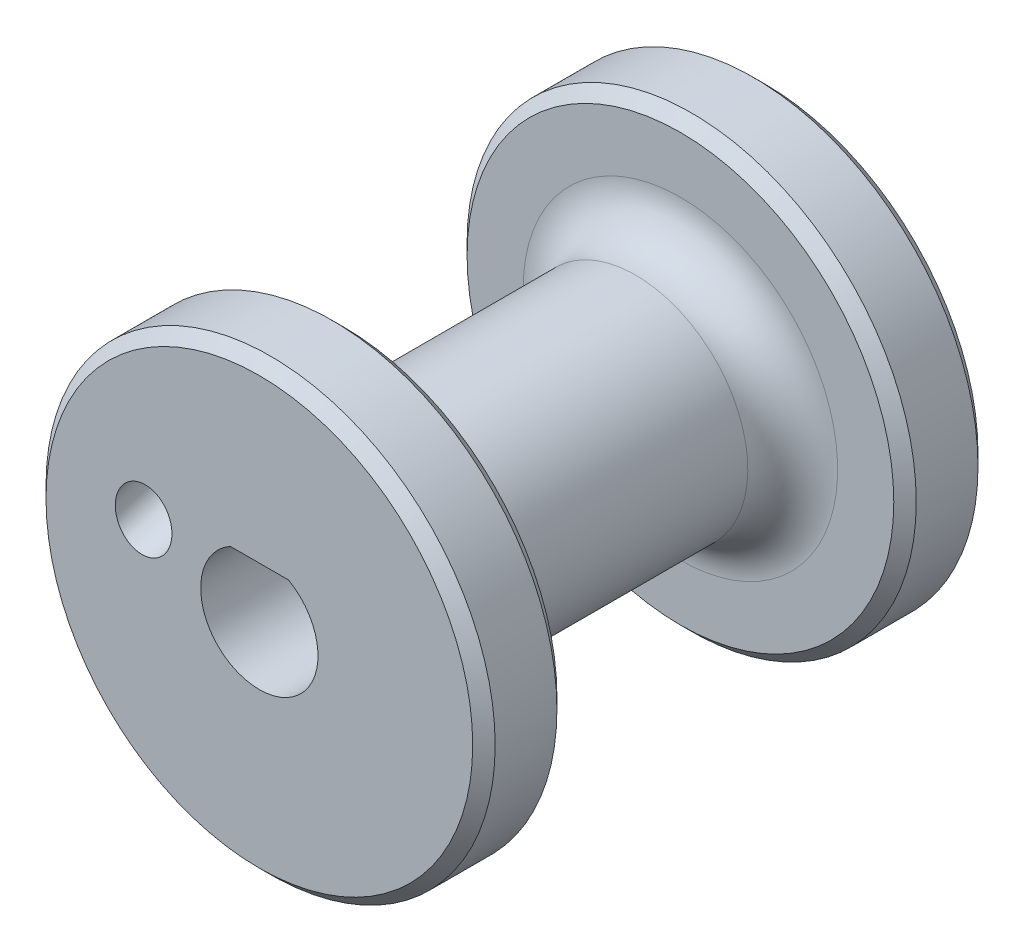
SolidWorks part; units mm, degrees
ref_plane "Front Plane" through (0, 0, 0) normal (0, 0, 1) x (1, 0, 0)
ref_plane "Top Plane" through (0, 0, 0) normal (0, 1, 0) x (1, 0, 0)
ref_plane "Right Plane" through (0, 0, 0) normal (1, 0, 0) x (0, 0, -1)
sketch "Sketch1" plane through (0, 0, 0) normal (0, 0, 1) x (1, 0, 0)
  circle A0 centre (0, 0) radius 3.3175
  circle A1 centre (0, 0) radius 6.35
  dimension "D1" = 6.635
  dimension "D2" = 12.7
extrude "Boss-Extrude1" add sketch "Sketch1" along normal blind 9.525 and the other way blind 9.525 contours A1 A0 region at (-6.1704, 0, 0)
sketch "Sketch2" plane through (0, 0, -9.525) normal (0, 0, -1) x (-1, 0, 0)
  circle A0 centre (0, 0) radius 12.7
  circle A1 centre (0, 0) radius 6.35 construction
  circle A2 centre (0, 0) radius 6.35 construction
  circle A3 centre (0, 0) radius 3.3175 construction
  circle A4 centre (0, 0) radius 3.3175
  circle M3 centre (0, 0) radius 3.3175
  circle M4 centre (0, 0) radius 6.35
  dimension "D1" = 6.35
extrude "Boss-Extrude3" add sketch "Sketch2" along normal blind 4.7625 contours M4 M3 | A0 M4 region at (12.3408, 0, -9.525) region at (6.1704, 0, -9.525)
mirror "Mirror1" about plane through (0, 0, 0) normal (0, 0, 1) of "Boss-Extrude3"
sketch "Sketch3" plane through (0, 0, -14.2875) normal (0, 0, -1) x (-1, 0, 0)
  circle A0 centre (0, 0) radius 3.3175 construction
  circle A1 centre (0, 0) radius 3.3175
extrude "Boss-Extrude4" add sketch "Sketch3" against normal through all
fillet "Fillet1" radius 2.54 2 edges at (6.35, 0, 9.525) (6.35, 0, -9.525)
chamfer "Chamfer1" distance 0.635 angle 45 4 edges at (-12.7, 0, -14.2875) (-12.7, 0, -9.525) (-12.7, 0, 9.525) (-12.7, 0, 14.2875)
sketch "Sketch4" plane through (0, 0, 14.2875) normal (0, 0, 1) x (1, 0, 0)
  line L0 (-1.651, 2.8775) -> (1.651, 2.8775)
  circle A3 centre (0, 0) radius 6.35
  circle A4 centre (0, 0) radius 6.35
  circle A5 centre (0, 0) radius 3.3175
  circle A6 centre (0, 0) radius 3.3175
  dimension "D1" = 0
  dimension "D3" = 3.302
  dimension "D2" = 0
extrude "Cut-Extrude1" cut sketch "Sketch4" against normal blind 13.97 contours L0 A6 region at (0, -0.0893, 14.2875)
sketch "Sketch5" plane through (0, 0, 14.2875) normal (0, 0, 1) x (1, 0, 0)
  point P0 (-6.5447, 1.737)
  point P1 (-6.5447, 1.737)
sketch3d "3DSketch1"
  point P0 (-5.8259, 4.2649, 8.8989)
ref_axis "Axis1" through (-5.8259, 4.2649, 8.8989) along (-0.1199, -0.4216, 0.8988)
ref_plane "Plane1" through (-6.5447, 1.737, 14.2875) normal (-0.1199, -0.4216, 0.8988) x (0.9928, -0.0509, 0.1085)
sketch "Sketch6" plane through (-6.5447, 1.737, 14.2875) normal (-0.1199, -0.4216, 0.8988) x (0.9928, -0.0509, 0.1085)
  circle A0 centre (0, 0) radius 1.5875
  dimension "D1" = 3.175
extrude "Cut-Extrude2" cut sketch "Sketch6" against normal up to next and the other way up to next
